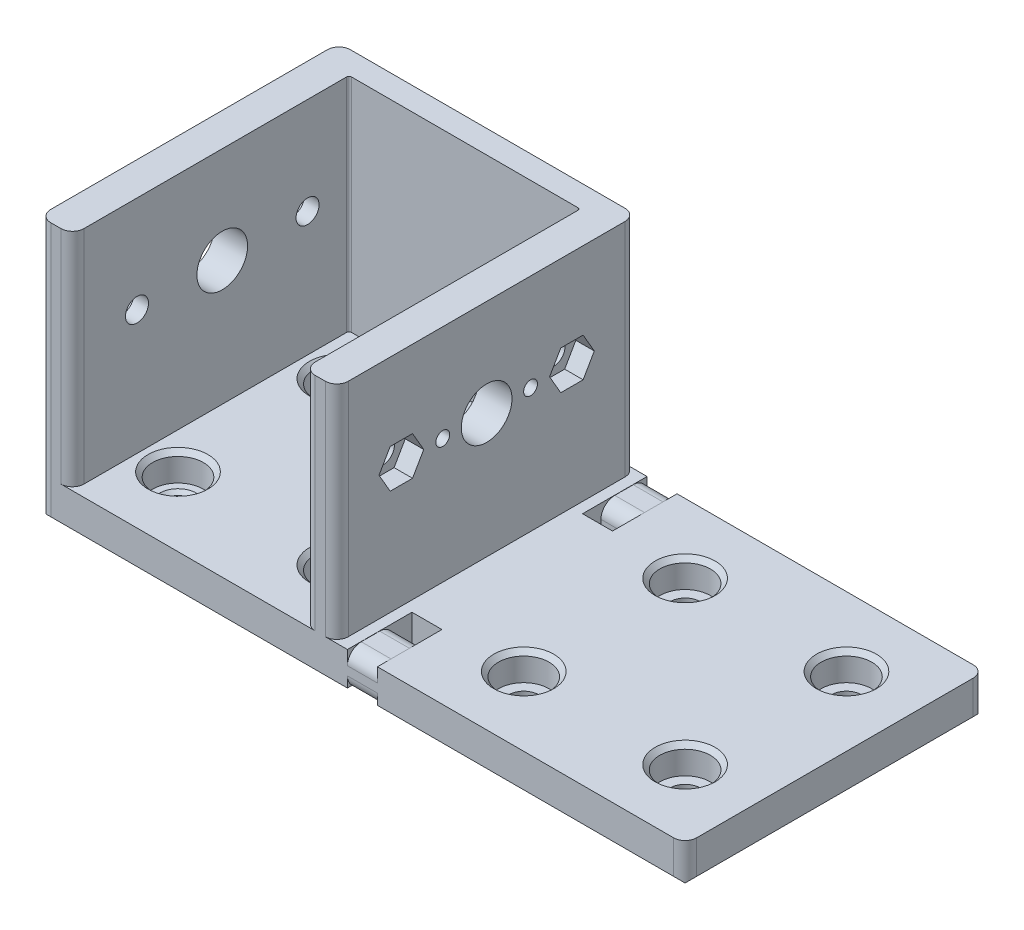
SolidWorks part; units mm, degrees
ref_plane "Front Plane" through (0, 0, 0) normal (0, 0, 1) x (1, 0, 0)
ref_plane "Top Plane" through (0, 0, 0) normal (0, 1, 0) x (1, 0, 0)
ref_plane "Right Plane" through (0, 0, 0) normal (1, 0, 0) x (0, 0, -1)
sketch "Sketch1" plane through (0, 0, 0) normal (0, 1, 0) x (1, 0, 0)
  line L0 (0, 14.013) -> (0, -13.1268) construction
  line L1 (-3.8771, 0) -> (4.5418, 0) construction
  line L2 (-37.5, 17.5) -> (-37.5, -17.5) construction
  line L3 (70, 32.5) -> (-70, 32.5)
  line L4 (-70, 32.5) -> (-70, -32.5)
  line L5 (70, -32.5) -> (-70, -32.5)
  line L6 (70, 32.5) -> (70, -32.5)
  circle A0 centre (-37.5, 0) radius 10 construction
  circle A1 centre (-55, 17.5) radius 3.25
  circle A2 centre (-55, -17.5) radius 3.25
  circle A3 centre (-20, -17.5) radius 3.25
  circle A4 centre (-20, 17.5) radius 3.25
  circle A5 centre (55, -17.5) radius 3.25
  circle A6 centre (20, -17.5) radius 3.25
  circle A7 centre (20, 17.5) radius 3.25
  circle A8 centre (37.5, 0) radius 10 construction
  circle A9 centre (55, 17.5) radius 3.25
  circle A10 centre (-55, 17.5) radius 5.5 construction
  circle A11 centre (-20, 17.5) radius 5.5 construction
  circle A12 centre (-20, -17.5) radius 5.5 construction
  circle A13 centre (-55, -17.5) radius 5.5 construction
  circle A14 centre (20, -17.5) radius 5.5 construction
  circle A15 centre (20, 17.5) radius 5.5 construction
  circle A16 centre (55, 17.5) radius 5.5 construction
  circle A17 centre (55, -17.5) radius 5.5 construction
  point P19 (-70, 0)
  point P33 (0, -32.5)
  point P34 (0, 32.5)
  dimension "D1" = 20
  dimension "D2" = 6.5
  dimension "D10" = 11
  dimension "D3" = 35
  dimension "D4" = 35
  dimension "D5" = 75
  dimension "D6" = 15
  dimension "D7" = 15
  dimension "D8" = 65
  dimension "D9" = 140
extrude "Boss-Extrude1" add sketch "Sketch1" along normal blind 8
sketch "Sketch5" plane through (0, 8, 0) normal (0, 1, 0) x (1, 0, 0)
  circle A0 centre (-55, 17.5) radius 5.5
  circle A1 centre (-20, 17.5) radius 5.5
  circle A2 centre (20, 17.5) radius 5.5
  circle A3 centre (55, 17.5) radius 5.5
  circle A4 centre (55, -17.5) radius 5.5
  circle A5 centre (20, -17.5) radius 5.5
  circle A6 centre (-20, -17.5) radius 5.5
  circle A7 centre (-55, -17.5) radius 5.5
  dimension "D1" = 11
extrude "Cut-Extrude1" cut sketch "Sketch5" against normal blind 6
sketch "Sketch3" plane through (-70, 0, 0) normal (-1, 0, 0) x (0, 0, 1)
  line L0 (-32.5, 0) -> (-32.5, 8)
  line L1 (-32.5, 8) -> (32.5, 8) construction
  line L2 (-32.5, 8) -> (32.5, 8)
  line L3 (32.5, 8) -> (32.5, 0)
  line L4 (32.5, 0) -> (-32.5, 0)
extrude "Boss-Extrude3" add sketch "Sketch3" along normal blind 0.1
sketch "Sketch4" plane through (0, 8, 0) normal (0, 1, 0) x (1, 0, 0)
  line L0 (-70.1, 32.5) -> (-70.1, -32.5)
  line L1 (-70.1, -32.5) -> (-62.9, -32.5)
  line L3 (-62.9, -32.5) -> (-62.9, 32.5)
  line L5 (-62.9, 32.5) -> (-70.1, 32.5)
  line L12 (-5.55, 32.5) -> (-12.75, 32.5)
  line L13 (-12.75, 32.5) -> (-12.75, -32.5)
  line L14 (-12.75, -32.5) -> (-5.55, -32.5)
  line L15 (-5.55, 32.5) -> (-5.55, -32.5)
  line L16 (-70.1, -32.5) -> (-70.1, 32.5) construction
  line L17 (0, 0) -> (-70.1, 0) construction
  dimension "D1" = 7.2
  dimension "D2" = 50.15
  dimension "D6" = 7.2
extrude "Boss-Extrude4" add sketch "Sketch4" along normal blind 48
sketch "Sketch6" plane through (-70.1, 0, 0) normal (-1, 0, 0) x (0, 0, 1)
  line L0 (-32.5, 8) -> (32.5, 8) construction
  line L1 (-32.5, 56) -> (-32.5, 0) construction
  line L2 (32.5, 0) -> (32.5, 56) construction
  line L3 (-32.5, 0) -> (32.5, 0) construction
  line L4 (0, 56) -> (0, 8) construction
  line L5 (-32.5, 56) -> (32.5, 56) construction
  circle A0 centre (0, 35) radius 5.5
  circle A1 centre (-18.5, 35) radius 2.5
  circle A2 centre (18.5, 35) radius 2.5
  point P13 (0, 30.5)
  point P15 (0, 0)
  point P21 (0, 0)
  point P22 (0, 0)
  point P23 (0, 0)
  dimension "D2" = 11
  dimension "D3" = 5
  dimension "D1" = 8
  dimension "D4" = 37
  dimension "D5" = 35
extrude "Cut-Extrude2" cut sketch "Sketch6" against normal through all both and the other way through all
sketch "Sketch8" plane through (-5.55, 0, 0) normal (1, 0, 0) x (0, 0, -1)
  line L0 (-9.525, 35) -> (9.525, 35) construction
  circle A0 centre (0, 35) radius 9.525 construction
  circle A1 centre (9.525, 35) radius 1.5
  circle A2 centre (-9.525, 35) radius 1.5
  dimension "D1" = 19.05
  dimension "D2" = 3
extrude "Cut-Extrude3" cut sketch "Sketch8" against normal blind 10
sketch "Sketch9" plane through (-5.55, 0, 0) normal (1, 0, 0) x (0, 0, -1)
  line L0 (-32.5, 8) -> (32.5, 8) construction
  line L1 (23.3497, 35) -> (20.9249, 39.2)
  line L2 (20.9249, 39.2) -> (16.0751, 39.2)
  line L3 (16.0751, 39.2) -> (13.6503, 35)
  line L4 (13.6503, 35) -> (16.0751, 30.8)
  line L5 (16.0751, 30.8) -> (20.9249, 30.8)
  line L6 (20.9249, 30.8) -> (23.3497, 35)
  line L7 (-13.6503, 35) -> (-16.0751, 39.2)
  line L8 (-16.0751, 39.2) -> (-20.9249, 39.2)
  line L9 (-20.9249, 39.2) -> (-23.3497, 35)
  line L10 (-23.3497, 35) -> (-20.9249, 30.8)
  line L11 (-20.9249, 30.8) -> (-16.0751, 30.8)
  line L12 (-16.0751, 30.8) -> (-13.6503, 35)
  circle A0 centre (18.5, 35) radius 4.2 construction
  circle A1 centre (-18.5, 35) radius 4.2 construction
  dimension "D1" = 8.4
  dimension "D2" = 8.4
extrude "Cut-Extrude4" cut sketch "Sketch9" against normal blind 4
sketch "Sketch11" plane through (-12.75, 0, 0) normal (-1, 0, 0) x (0, 0, 1)
  line L1 (12.525, 36.7321) -> (9.525, 38.4641)
  line L2 (9.525, 38.4641) -> (6.525, 36.7321)
  line L3 (6.525, 36.7321) -> (6.525, 33.2679)
  line L4 (6.525, 33.2679) -> (9.525, 31.5359)
  line L5 (9.525, 31.5359) -> (12.525, 33.2679)
  line L6 (12.525, 33.2679) -> (12.525, 36.7321)
  line L7 (-9.525, 38.4641) -> (-12.525, 36.7321)
  line L8 (-12.525, 36.7321) -> (-12.525, 33.2679)
  line L9 (-12.525, 33.2679) -> (-9.525, 31.5359)
  line L10 (-9.525, 31.5359) -> (-6.525, 33.2679)
  line L11 (-6.525, 33.2679) -> (-6.525, 36.7321)
  line L12 (-6.525, 36.7321) -> (-9.525, 38.4641)
  circle A0 centre (9.525, 35) radius 3 construction
  circle A1 centre (-9.525, 35) radius 3 construction
  point P10 (-6.525, 35)
  dimension "D1" = 6
  dimension "D2" = 6
extrude "Cut-Extrude6" cut sketch "Sketch11" against normal blind 3.5
sketch "Sketch12" plane through (-70.1, 0, 0) normal (-1, 0, 0) x (0, 0, 1)
  line L1 (-16.0751, 30.8) -> (-13.6503, 35)
  line L2 (-13.6503, 35) -> (-16.0751, 39.2)
  line L3 (-16.0751, 39.2) -> (-20.9249, 39.2)
  line L4 (-20.9249, 39.2) -> (-23.3497, 35)
  line L5 (-23.3497, 35) -> (-20.9249, 30.8)
  line L6 (-20.9249, 30.8) -> (-16.0751, 30.8)
  line L7 (20.9249, 30.8) -> (23.3497, 35)
  line L8 (23.3497, 35) -> (20.9249, 39.2)
  line L9 (20.9249, 39.2) -> (16.0751, 39.2)
  line L10 (16.0751, 39.2) -> (13.6503, 35)
  line L11 (13.6503, 35) -> (16.0751, 30.8)
  line L12 (16.0751, 30.8) -> (20.9249, 30.8)
  circle A0 centre (-18.5, 35) radius 4.2 construction
  circle A1 centre (18.5, 35) radius 4.2 construction
  dimension "D1" = 8.4
  dimension "D2" = 8.4
extrude "Cut-Extrude7" cut sketch "Sketch12" against normal blind 4
chamfer "Chamfer2" distance 1 angle 45 8 edges at (55, 8, -12) (55, 8, 23) (-55, 8, -12) (-55, 8, 23) (-20, 8, 23) (-20, 8, -12) (20, 8, -12) (20, 8, 23)
sketch "Sketch13" plane through (0, 8, 0) normal (0, 1, 0) x (1, 0, 0)
  line L0 (0, 32.5) -> (0, -32.5) construction
  line L1 (70, 32.5) -> (-5.55, 32.5) construction
  line L3 (-97.7834, 0) -> (132.9787, 0) construction
  line L4 (-3.25, 22.5) -> (3.25, 22.5)
  line L5 (3.25, 22.5) -> (3.25, 18.5)
  line L6 (3.25, 18.5) -> (-3.25, 18.5)
  line L7 (-3.25, 22.5) -> (-3.25, 18.5)
  line L9 (-3.25, -22.5) -> (-3.25, -18.5)
  line L10 (3.25, -18.5) -> (-3.25, -18.5)
  line L11 (3.25, -22.5) -> (3.25, -18.5)
  line L12 (-3.25, -22.5) -> (3.25, -22.5)
  point P11 (0, 22.5)
  point P12 (0, 18.5)
  dimension "D1" = 6.5
  dimension "D2" = 4
  dimension "D3" = 10
extrude "Cut-Extrude8" cut sketch "Sketch13" against normal blind 10
sketch "Sketch14" plane through (0, 8, 0) normal (0, 1, 0) x (1, 0, 0)
  line L0 (-3.25, 22.5) -> (-3.25, 32.5)
  line L2 (3.25, 22.5) -> (3.25, 32.5)
  line L3 (3.25, 32.5) -> (-3.25, 32.5)
  line L4 (-3.25, 22.5) -> (3.25, 22.5)
  line L5 (-3.25, -22.5) -> (-3.25, -32.5)
  line L7 (-3.25, -32.5) -> (3.25, -32.5)
  line L8 (3.25, -32.5) -> (3.25, -22.5)
  line L9 (3.25, -22.5) -> (-3.25, -22.5)
  line L10 (-5.55, -32.5) -> (70, -32.5) construction
  line L11 (70, 32.5) -> (-5.55, 32.5) construction
  point P3 (0, 0)
  point P11 (0, 0)
  point P12 (0, 0)
  point P16 (0, 0)
  point P17 (0, 0)
  point P18 (0, 0)
  point P21 (0, 0)
  point P22 (0, 0)
  point P24 (0, 0)
extrude "Cut-Extrude9" cut sketch "Sketch14" against normal blind 0.05
sketch "Sketch15" plane through (0, 0, 0) normal (0, -1, 0) x (1, 0, 0)
  line L0 (-3.25, 22.5) -> (-3.25, 32.5)
  line L1 (-70.1, 32.5) -> (70, 32.5) construction
  line L2 (-3.25, 32.5) -> (3.25, 32.5)
  line L3 (3.25, 32.5) -> (3.25, 22.5)
  line L4 (3.25, 22.5) -> (-3.25, 22.5)
  line L5 (-3.25, -22.5) -> (-3.25, -32.5)
  line L6 (-3.25, -32.5) -> (3.25, -32.5)
  line L7 (3.25, -32.5) -> (3.25, -22.5)
  line L8 (3.25, -22.5) -> (-3.25, -22.5)
extrude "Cut-Extrude10" cut sketch "Sketch15" against normal blind 0.05
fillet "Fillet9" radius 3 8 edges at (0, 0.05, 22.5) (0, 0.05, 32.5) (0, 7.95, 32.5) (0, 7.95, 22.5) (0, 7.95, -22.5) (0, 0.05, -22.5) (0, 0.05, -32.5) (0, 7.95, -32.5)
chamfer "Chamfer4" distance 0.75 angle 45 21 edges at (-3.25, 0, -25.5) (3.25, 0, -25.5) (0, 0, -18.5) (36.625, 0, -32.5) (70, 0, 0) (-3.25, 0, 25.5) (0, 0, 18.5) (3.25, 0, 25.5) (36.625, 0, 32.5) (-36.675, 0, -32.5) (-36.675, 0, 32.5) (-70.1, 0, 0) (-55, 2, 20.75) (-55, 0, 14.25) (-55, 0, -14.25) (-20, 0, -20.75) (-20, 0, 20.75) (20, 0, 14.25) (20, 0, -14.25) (55, 0, -20.75) (55, 0, 20.75)
sketch "Sketch20" plane through (0, 8, 0) normal (0, 1, 0) x (1, 0, 0)
  line L0 (-12.75, 32.5) -> (-12.75, -32.5) construction
  line L1 (-62.9, 32.5) -> (-12.75, 32.5)
  line L2 (-62.9, 32.5) -> (-62.9, 27.5)
  line L3 (-62.9, 27.5) -> (-12.75, 27.5)
  line L4 (-12.75, 32.5) -> (-12.75, 27.5)
  dimension "D1" = 5
extrude "Boss-Extrude6" add sketch "Sketch20" along normal blind 48
fillet "Fillet10" radius 2.5 8 edges at (-12.75, 32, 32.5) (-62.9, 32, 32.5) (-5.55, 32, 32.5) (-5.55, 32, -32.5) (-70.1, 28.375, -32.5) (-70.1, 28.375, 32.5) (70, 4.375, -32.5) (70, 4.375, 32.5)
fillet "Fillet11" radius 0.5 2 edges at (-62.9, 32, -27.5) (-12.75, 32, -27.5)
